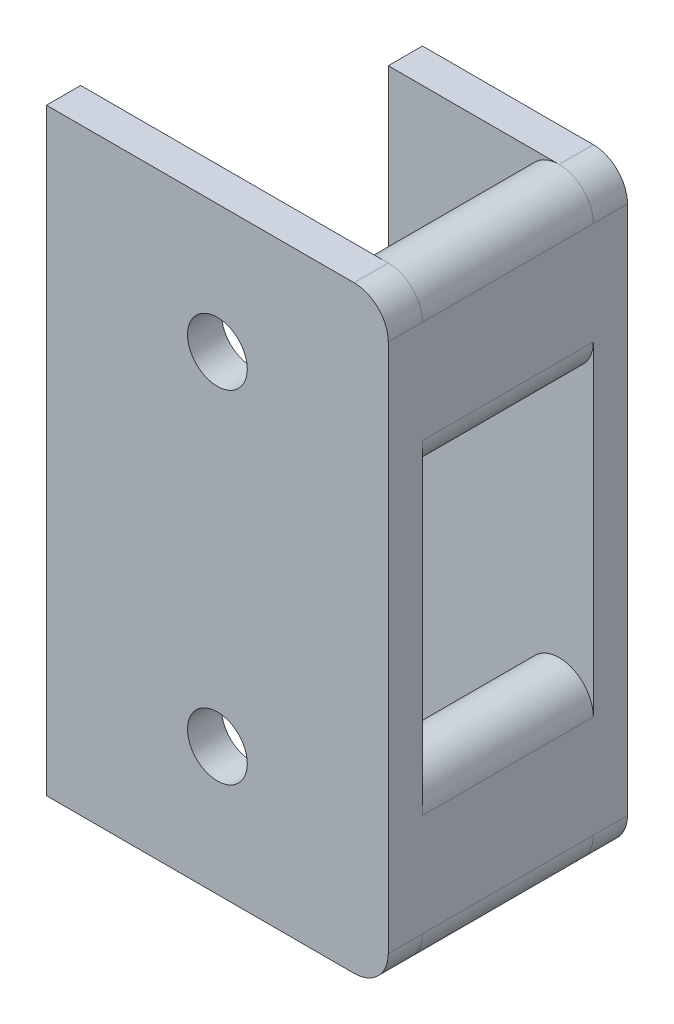
SolidWorks part; units mm, degrees
ref_plane "Plan de face" through (0, 0, 0) normal (0, 0, 1) x (1, 0, 0)
ref_plane "Plan de dessus" through (0, 0, 0) normal (0, 1, 0) x (1, 0, 0)
ref_plane "Plan de droite" through (0, 0, 0) normal (1, 0, 0) x (0, 0, -1)
sketch "Esquisse1" plane through (0, 0, 0) normal (0, 0, 1) x (1, 0, 0)
  line L0 (-6.6025, 20.2958) -> (3.3975, 20.2958) construction
  line L1 (3.3975, 2.7958) -> (-16.6025, 2.7958)
  line L2 (3.3975, 2.7958) -> (3.3975, 37.7958)
  line L3 (3.3975, 37.7958) -> (-16.6025, 37.7958)
  line L4 (-16.6025, 2.7958) -> (-16.6025, 37.7958)
  line L8 (-6.6025, 30.2958) -> (-6.6025, 10.2958) construction
  circle A1 centre (-6.6025, 30.2958) radius 1.75
  circle A2 centre (-6.6025, 10.2958) radius 1.75
  dimension "D2" = 3.5
  dimension "D1" = 20
  dimension "D3" = 10
  dimension "D4" = 20
  dimension "D5" = 35
extrude "Boss.-Extru.1" add sketch "Esquisse1" against normal blind 2
sketch "Esquisse2" plane through (0, 0, -2) normal (0, 0, -1) x (-1, 0, 0)
  line L0 (-1.3975, 35.7958) -> (-1.3975, 29.7958) construction
  line L1 (0.6025, 35.7958) -> (0.6025, 29.7958)
  line L2 (-3.3975, 35.7958) -> (-3.3975, 29.7958)
  line L3 (-3.3975, 2.7958) -> (-3.3975, 37.7958) construction
  line L4 (-3.3975, 20.2958) -> (16.6025, 20.2958) construction
  line L5 (16.6025, 37.7958) -> (16.6025, 2.7958) construction
  line L6 (-1.3975, 4.7958) -> (-1.3975, 10.7958) construction
  line L7 (0.6025, 4.7958) -> (0.6025, 10.7958)
  line L8 (-3.3975, 4.7958) -> (-3.3975, 10.7958)
  arc A0 (0.6025, 35.7958) -> (-3.3975, 35.7958) centre (-1.3975, 35.7958) ccw
  arc A1 (-3.3975, 29.7958) -> (0.6025, 29.7958) centre (-1.3975, 29.7958) ccw
  arc A2 (0.6025, 4.7958) -> (-3.3975, 4.7958) centre (-1.3975, 4.7958) cw
  arc A3 (-3.3975, 10.7958) -> (0.6025, 10.7958) centre (-1.3975, 10.7958) cw
  point P2 (-1.3975, 32.7958)
  point P15 (-1.3975, 7.7958)
  dimension "D1" = 2
  dimension "D2" = 6
  dimension "D3" = 12.5
extrude "Boss.-Extru.2" add sketch "Esquisse2" along normal blind 10
sketch "Esquisse3" plane through (0, 0, -12) normal (0, 0, -1) x (-1, 0, 0)
  line L1 (-3.3975, 37.7958) -> (8.6025, 37.7958)
  line L2 (-3.3975, 37.7958) -> (-3.3975, 2.7958)
  line L3 (-3.3975, 2.7958) -> (8.6025, 2.7958)
  line L4 (8.6025, 37.7958) -> (8.6025, 2.7958)
  line L5 (16.6025, 2.7958) -> (-1.3975, 2.7958) construction
  dimension "D1" = 12
extrude "Boss.-Extru.3" add sketch "Esquisse3" along normal blind 2
fillet "Congé1" radius 2 4 edges at (3.3975, 2.7958, -1) (3.3975, 37.7958, -13) (3.3975, 2.7958, -13) (3.3975, 37.7958, -1)
